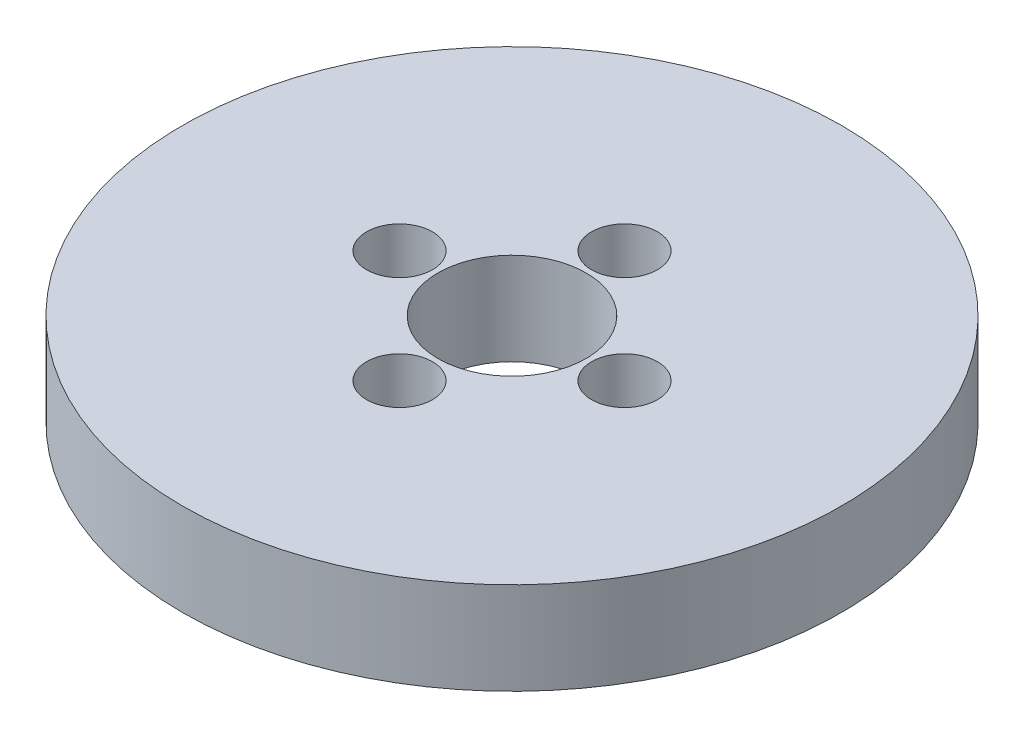
SolidWorks part; units mm, degrees
ref_plane "Front Plane" through (0, 0, 0) normal (0, 0, 1) x (1, 0, 0)
ref_plane "Top Plane" through (0, 0, 0) normal (0, 1, 0) x (1, 0, 0)
ref_plane "Right Plane" through (0, 0, 0) normal (1, 0, 0) x (0, 0, -1)
sketch "Sketch1" plane through (0, 0, 0) normal (0, 1, 0) x (1, 0, 0)
  circle A0 centre (0, 0) radius 100
  dimension "FLANGE_OD" = 200
extrude "Boss-Extrude1" add sketch "Sketch1" along normal blind 28
sketch "Sketch2" plane through (0, 0, 0) normal (0, 1, 0) x (1, 0, 0)
  circle A0 centre (0, 0) radius 22.5
  dimension "BORE_D" = 45
extrude "Cut-Extrude1" cut sketch "Sketch2" along normal through all
sketch "Sketch3" plane through (0, 28, 0) normal (0, 1, 0) x (1, 0, 0)
  circle A0 centre (0, 0) radius 34.137 construction
  circle A1 centre (-34.137, 0) radius 10
  dimension "BOLT_D" = 20
  dimension "BOLT_PCD" = 68.2741
extrude "Cut-Extrude2" cut sketch "Sketch3" against normal blind 22.8189
pattern_circular "CirPattern1" count 4 over 360 about axis through (0, 0, 0) along (0, 1, 0) of "Cut-Extrude2"
